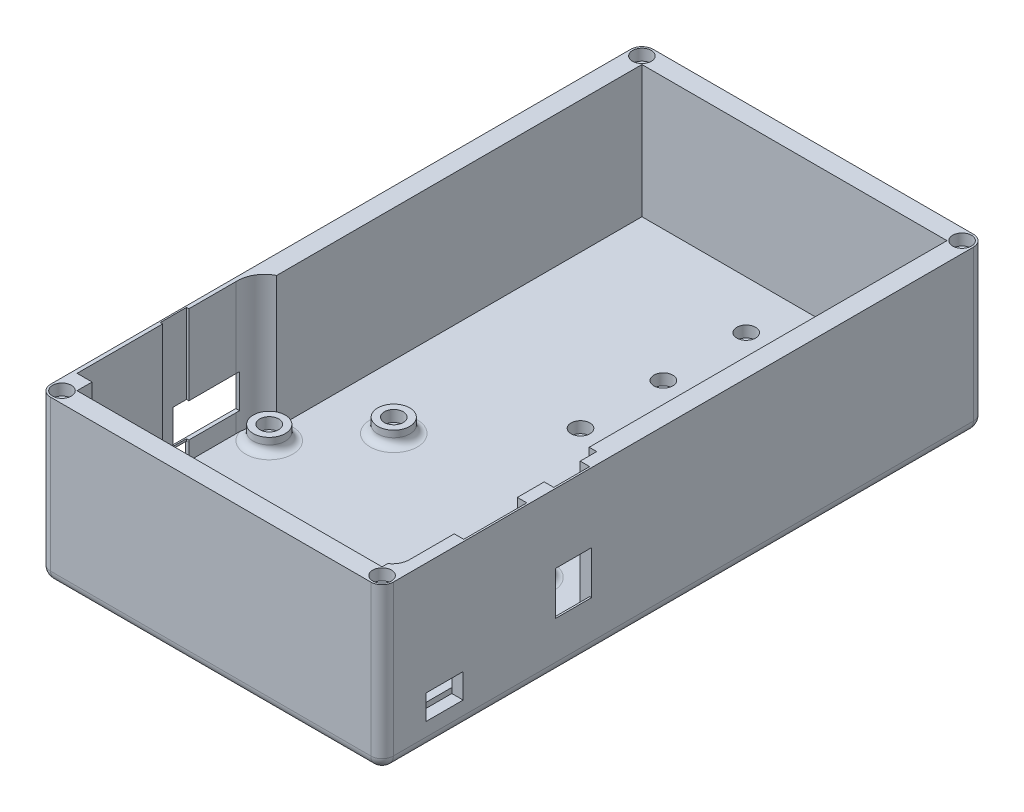
SolidWorks part; units mm, degrees
ref_plane "Front Plane" through (0, 0, 0) normal (0, 0, 1) x (1, 0, 0)
ref_plane "Top Plane" through (0, 0, 0) normal (0, 1, 0) x (1, 0, 0)
ref_plane "Right Plane" through (0, 0, 0) normal (1, 0, 0) x (0, 0, -1)
sketch "Sketch1" plane through (0, 0, 0) normal (0, 1, 0) x (1, 0, 0)
  line L1 (-45.5, -80) -> (45.5, -80)
  line L2 (-45.5, -80) -> (-45.5, 80)
  line L3 (-45.5, 80) -> (45.5, 80)
  line L4 (45.5, -80) -> (45.5, 80)
  line L5 (-45.5, -80) -> (45.5, 80) construction
  line L6 (-45.5, 80) -> (45.5, -80) construction
  point P0 (0, 0)
  dimension "D1" = 91
  dimension "D2" = 160
extrude "Boss-Extrude1" add sketch "Sketch1" along normal blind 8
sketch "Sketch2" [suppressed] plane through (0, 0, 0) normal (0, -1, 0) x (1, 0, 0)
  line L0 (-45.038, 58.829) -> (45.038, 58.829) construction
  line L1 (-50.038, -63.829) -> (50.038, -63.829)
  line L2 (-50.038, -63.829) -> (-50.038, 63.829)
  line L3 (-50.038, 63.829) -> (50.038, 63.829)
  line L4 (50.038, -63.829) -> (50.038, 63.829)
  line L5 (-50.038, -63.829) -> (50.038, 63.829) construction
  line L6 (-50.038, 63.829) -> (50.038, -63.829) construction
  line L8 (45.038, 58.829) -> (45.038, -58.829) construction
  line L10 (-45.038, -58.829) -> (45.038, -58.829)
  line L11 (-45.038, -58.829) -> (-45.038, 58.829)
  line L12 (-45.038, 58.829) -> (45.038, 58.829)
  line L13 (45.038, -58.829) -> (45.038, 58.829)
  line L14 (-45.038, -58.829) -> (45.038, 58.829) construction
  line L15 (-45.038, 58.829) -> (45.038, -58.829) construction
  point P0 (0, 0)
  point P8 (0, 0)
  dimension "D1" = 5
  dimension "D3" = 5
sketch "Sketch4" plane through (0, 8, 0) normal (0, 1, 0) x (1, 0, 0)
  line L0 (45.5, -80) -> (45.5, 80) construction
  line L1 (-45.5, 80) -> (-40.5, 80)
  line L2 (-45.5, 80) -> (-45.5, -22)
  line L3 (-45.5, -22) -> (-40.5, -22)
  line L4 (-40.5, 80) -> (-40.5, -22)
  line L5 (45.5, 80) -> (40.5, 80)
  line L6 (45.5, 80) -> (45.5, -20)
  line L7 (45.5, -20) -> (40.5, -20)
  line L8 (40.5, 80) -> (40.5, -20)
  line L9 (-40.5, 80) -> (40.5, 80)
  line L10 (-40.5, 80) -> (-40.5, 75)
  line L11 (-40.5, 75) -> (40.5, 75)
  line L12 (40.5, 80) -> (40.5, 75)
  line L13 (-45.5, -80) -> (45.5, -80)
  line L14 (-45.5, -80) -> (-45.5, -75)
  line L15 (-45.5, -75) -> (45.5, -75)
  line L16 (45.5, -80) -> (45.5, -75)
  line L18 (-45.5, -80) -> (-40.5, -80)
  line L19 (-45.5, -80) -> (-45.5, -71)
  line L20 (-45.5, -71) -> (-40.5, -71)
  line L21 (-40.5, -80) -> (-40.5, -71)
  line L22 (45.5, -80) -> (40.5, -80)
  line L23 (45.5, -80) -> (45.5, -73.5)
  line L24 (45.5, -73.5) -> (40.5, -73.5)
  line L25 (40.5, -80) -> (40.5, -73.5)
  line M11 (45.5, -80) -> (45.5, 80)
  line M12 (45.5, 80) -> (-45.5, 80)
  line M13 (-45.5, 80) -> (-45.5, -80)
  line M14 (-45.5, -80) -> (45.5, -80)
  dimension "D1" = 102
  dimension "D2" = 100
  dimension "D3" = 5
  dimension "D4" = 5
  dimension "D5" = 5
  dimension "D6" = 5
  dimension "D7" = 9
  dimension "D8" = 6.5
extrude "Boss-Extrude4" add sketch "Sketch4" along normal blind 35 contours L4 L3 M12 M13 | L4 L11 L8 M12 | L8 L7 M12 M11 | L13 L25 L15 L21 | L15 L21 L20 M13 | L21 L15 M14 M13 | L23 L24 L25 L22 region at (-43, 8, -29) region at (0, 8, -77.5) region at (43, 8, -30) region at (-43, 8, 73) region at (-43, 8, 77.5) region at (0, 8, 77.5)
sketch "Sketch5" plane through (0, 8, 0) normal (0, 1, 0) x (1, 0, 0)
  line L0 (-23.6185, -7.7762) -> (23.6185, -7.7762) construction
  line L1 (45.5, 80) -> (-45.5, 80) construction
  line L2 (40.5, 75) -> (40.5, -20) construction
  line L4 (-40.5, 75) -> (-40.5, -22) construction
  line L12 (45.5, -80) -> (-45.5, -80) construction
  line L13 (45.5, -73.5) -> (45.5, -20) construction
  circle A0 centre (23.6185, -7.7762) radius 4.25
  circle A1 centre (-23.6185, -7.7762) radius 4.25
  circle A2 centre (27.54, -22.78) radius 4.25
  circle A3 centre (27.54, -71.04) radius 4.25
  circle A4 centre (-38.5, -67.865) radius 4.25
  circle A5 centre (-38.5, -25.958) radius 4.25
  point P17 (-38.5, -25.958)
  point P18 (-38.5, -67.865)
  dimension "D4" = 8.5
  dimension "D5" = 8.5
  dimension "D10" = 8.5
  dimension "D1" = 87.7762
  dimension "D2" = 16.8815
  dimension "D3" = 16.8815
  dimension "D6" = 8.96
  dimension "D7" = 17.96
  dimension "D8" = 57.22
extrude "Boss-Extrude5" add sketch "Sketch5" along normal blind 3.75
sketch "Sketch6" plane through (0, 8, 0) normal (0, 1, 0) x (1, 0, 0)
  line L0 (-45.5, -22) -> (-45.5, -71)
  line L1 (-45.5, -71) -> (-44.49, -71)
  line L2 (-45.5, -71) -> (-41.3695, -71) construction
  line L3 (-44.49, -71) -> (-44.49, -28.77)
  line L4 (-45.5, -22) -> (-40.5, -22)
  line L5 (45.5, -73.5) -> (45.5, -20)
  line L6 (45.5, -20) -> (42.5, -20)
  line L7 (45.5, -20) -> (40.5, -20) construction
  line L8 (42.5, -20) -> (42.5, -69.77)
  line L9 (45.5, -73.5) -> (40.5, -73.5) construction
  line L10 (45.5, -73.5) -> (40.5, -73.5)
  arc A0 (-40.5, -22) -> (-44.49, -28.77) centre (-37.3075, -28.4423) ccw
  arc A1 (40.5, -73.5) -> (42.5, -69.77) centre (37.8806, -69.6943) ccw
  dimension "D3" = 7.19
  dimension "D6" = 4.62
  dimension "D1" = 6.77
  dimension "D2" = 1.01
  dimension "D4" = 3
  dimension "D5" = 3.73
extrude "Boss-Extrude6" add sketch "Sketch6" along normal up to surface (35 mm away) up to face at (0, 43, -28.25)
sketch "Sketch7" plane through (0, 43, 0) normal (0, 1, 0) x (1, 0, 0)
  line L0 (42.5, -20) -> (42.5, -69.77) construction
  line L1 (42.5, -24.39) -> (45.02, -24.39)
  line L2 (42.5, -24.39) -> (42.5, -33.94)
  line L3 (42.5, -33.94) -> (45.02, -33.94)
  line L4 (45.02, -24.39) -> (45.02, -33.94)
  line L5 (42.5, -20) -> (42.5, -69.77) construction
  line L6 (42.5, -41.07) -> (45.02, -41.07)
  line L7 (42.5, -41.07) -> (42.5, -57.83)
  line L8 (42.5, -57.83) -> (45.02, -57.83)
  line L9 (45.02, -41.07) -> (45.02, -57.83)
  line L10 (42.5, -20) -> (40.5, -20) construction
  line L11 (-44.49, -71) -> (-44.49, -28.77) construction
  line L12 (-44.49, -41.32) -> (-45.12, -41.32)
  line L13 (-44.49, -41.32) -> (-44.49, -48.27)
  line L14 (-44.49, -48.27) -> (-45.12, -48.27)
  line L15 (-45.12, -41.32) -> (-45.12, -48.27)
  line L16 (-45.5, 80) -> (-45.5, -80) construction
  dimension "D1" = 2.52
  dimension "D2" = 9.55
  dimension "D3" = 4.39
  dimension "D4" = 2.52
  dimension "D5" = 16.76
  dimension "D6" = 15.67
  dimension "D7" = 0.38
  dimension "D8" = 6.95
  dimension "D9" = 19.32
extrude "Cut-Extrude1" cut sketch "Sketch7" against normal up to surface (35 mm away) up to face at (-38.5, 8, 21.708)
sketch "Sketch8" plane through (0, 8, 0) normal (0, 1, 0) x (1, 0, 0)
  line L0 (-40.5, 75) -> (40.5, 75) construction
  circle A0 centre (0, 62.189) radius 2.5
  circle A1 centre (0, 40.189) radius 2.5
  circle A2 centre (0, 18.19) radius 2.5
  dimension "D1" = 5
  dimension "D2" = 12.811
  dimension "D3" = 34.811
  dimension "D4" = 56.81
extrude "Cut-Extrude2" cut sketch "Sketch8" against normal blind 3
sketch "Sketch9" plane through (0, 11.75, 0) normal (0, 1, 0) x (1, 0, 0)
  circle A0 centre (-23.6185, -7.7762) radius 2.5
  circle A1 centre (23.6185, -7.7762) radius 2.5
  circle A2 centre (27.54, -22.78) radius 2.5
  circle A3 centre (-38.5, -25.958) radius 2.5
  circle A4 centre (-38.5, -67.865) radius 2.5
  circle A5 centre (27.54, -71.04) radius 2.5
  dimension "D1" = 5
extrude "Cut-Extrude3" cut sketch "Sketch9" against normal blind 3
fillet "Fillet2" radius 2 6 edges at (-36.0459, 8, 64.3952) (27.54, 8, 66.79) (-38.5, 8, 21.708) (27.54, 8, 18.53) (23.6185, 8, 3.5262) (-23.6185, 8, 3.5262)
sketch "Sketch10" plane through (45.5, 0, 0) normal (1, 0, 0) x (0, 0, -1)
  line L0 (-80, 43) -> (-80, 0) construction
  line L1 (-68.38, 13.15) -> (-58.48, 13.15)
  line L2 (-68.38, 13.15) -> (-68.38, 6.6)
  line L3 (-68.38, 6.6) -> (-58.48, 6.6)
  line L4 (-58.48, 13.15) -> (-58.48, 6.6)
  line L5 (-33.89, 24.6) -> (-24.39, 24.6)
  line L6 (-33.89, 24.6) -> (-33.89, 13.1)
  line L7 (-33.89, 13.1) -> (-24.39, 13.1)
  line L8 (-24.39, 24.6) -> (-24.39, 13.1)
  line L9 (-80, 0) -> (80, 0) construction
  dimension "D1" = 9.9
  dimension "D2" = 6.55
  dimension "D3" = 11.62
  dimension "D4" = 6.6
  dimension "D5" = 9.5
  dimension "D6" = 11.5
  dimension "D7" = 13.1
  dimension "D8" = 55.61
extrude "Cut-Extrude4" cut sketch "Sketch10" against normal blind 3
sketch "Sketch11" plane through (-45.5, 0, 0) normal (-1, 0, 0) x (0, 0, 1)
  line L0 (80, 43) -> (80, 0) construction
  line L1 (62.35, 11.78) -> (50.32, 11.78)
  line L2 (62.35, 11.78) -> (62.35, 10.4)
  line L3 (62.35, 10.4) -> (50.32, 10.4)
  line L4 (50.32, 11.78) -> (50.32, 10.4)
  line L5 (41.21, 8.85) -> (48.42, 8.85)
  line L6 (41.21, 8.85) -> (41.21, 12.25)
  line L7 (41.21, 12.25) -> (48.42, 12.25)
  line L8 (48.42, 8.85) -> (48.42, 12.25)
  line L9 (-80, 0) -> (80, 0) construction
  line L10 (36.35, 21.28) -> (36.35, 13.37) construction
  line L12 (28.7, 21.28) -> (28.7, 13.37)
  line L14 (44, 21.28) -> (44, 13.37)
  line L16 (27.85, 12.825) -> (44.85, 12.825)
  line L17 (27.85, 12.825) -> (27.85, 21.825)
  line L18 (27.85, 21.825) -> (44.85, 21.825)
  line L19 (44.85, 12.825) -> (44.85, 21.825)
  line L20 (27.85, 12.825) -> (44.85, 21.825) construction
  line L21 (27.85, 21.825) -> (44.85, 12.825) construction
  point P18 (36.35, 17.325)
  point P19 (36.35, 17.325)
  dimension "D1" = 7.21
  dimension "D2" = 3.4
  dimension "D3" = 12.03
  dimension "D4" = 1.38
  dimension "D5" = 31.58
  dimension "D6" = 17.65
  dimension "D7" = 8.85
  dimension "D8" = 10.4
  dimension "D9" = 15.3
  dimension "D10" = 7.91
  dimension "D11" = 36
  dimension "D13" = 17
  dimension "D14" = 9
extrude "Cut-Extrude5" cut sketch "Sketch11" against normal blind 3 contours L5 L8 L7 L6 | L1 L4 L3 L2 | L16 L19 L18 L17 region at (-45.5, 11.09, 56.335) region at (-45.5, 10.55, 44.815) region at (-45.5, 17.325, 36.35)
sketch "Sketch12" plane through (0, 43, 0) normal (0, 1, 0) x (1, 0, 0)
  line L0 (45.5, 80) -> (-45.5, 80) construction
  line L1 (45.5, -80) -> (45.5, 80) construction
  line L2 (-45.5, 80) -> (-45.5, -80) construction
  line L3 (45.5, -80) -> (-45.5, -80) construction
  circle A0 centre (-42.5, 77) radius 2.5
  circle A1 centre (42.5, 77) radius 2.5
  circle A2 centre (-42.5, -77) radius 2.5
  circle A3 centre (42.5, -77) radius 2.5
  dimension "D1" = 5
  dimension "D2" = 3
  dimension "D3" = 3
  dimension "D4" = 3
  dimension "D5" = 3
  dimension "D6" = 3
  dimension "D7" = 3
  dimension "D8" = 3
  dimension "D9" = 3
extrude "Cut-Extrude6" cut sketch "Sketch12" against normal blind 3
fillet "Fillet3" radius 3 8 edges at (45.5, 21.5, 80) (45.5, 21.5, -80) (-45.5, 21.5, -80) (-45.5, 21.5, 80) (0, 0, 80) (-45.5, 0, 0) (45.5, 0, 0) (0, 0, -80)
